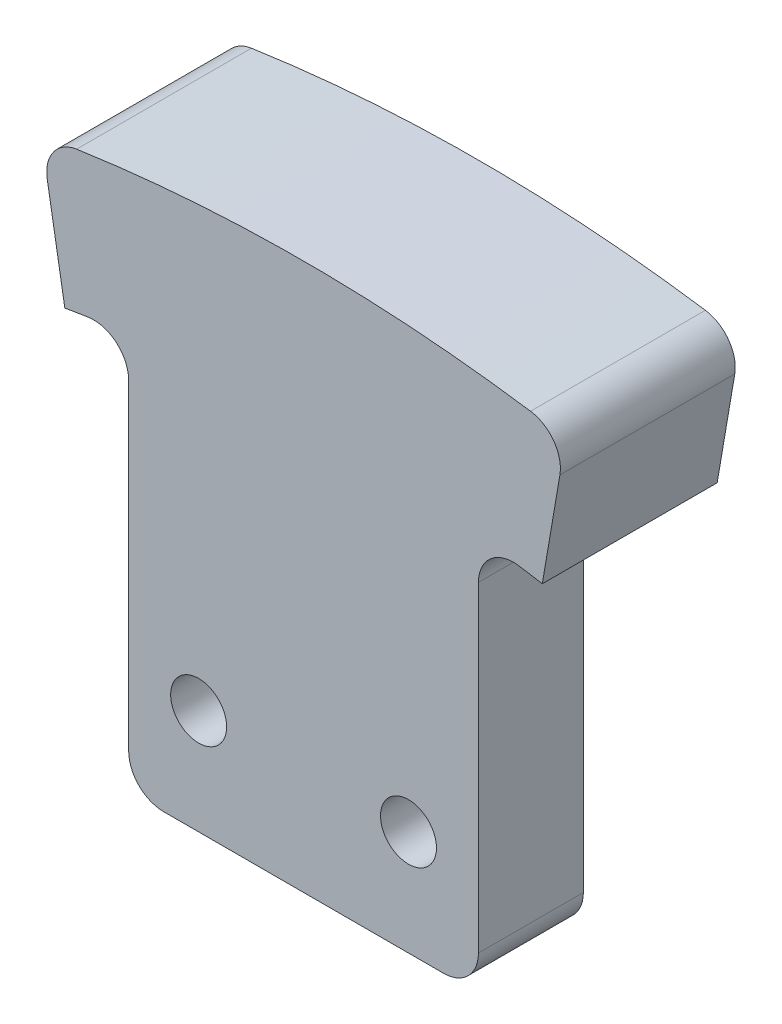
SolidWorks part; units mm, degrees
material "45#"
ref_plane "前视基准面" through (0, 0, 0) normal (0, 0, 1) x (1, 0, 0)
ref_plane "上视基准面" through (0, 0, 0) normal (0, 1, 0) x (1, 0, 0)
ref_plane "右视基准面" through (0, 0, 0) normal (1, 0, 0) x (0, 0, -1)
sketch "草图1" plane through (0, 0, 0) normal (0, 0, 1) x (1, 0, 0)
  line L1 (-5, -7.5) -> (5, -7.5)
  line L2 (-5, -7.5) -> (-5, 7.5)
  line L5 (-5, 7.5) -> (5, 7.5)
  line L6 (5, -7.5) -> (5, 7.5)
  line L7 (-5, -7.5) -> (5, 7.5) construction
  line L8 (-5, 7.5) -> (5, -7.5) construction
  point P0 (0, 0)
  dimension "D1" = 15
  dimension "D2" = 10
extrude "凸台-拉伸1" add sketch "草图1" along normal blind 3
hole_wizard "M2 螺纹孔1" positions "草图4" profile "草图5" tap size "M2" standard "GB" end condition through all
sketch "草图4" plane through (0, 0, 3) normal (0, 0, 1) x (1, 0, 0)
  line L0 (0, -7.5) -> (0, -4.5) construction
  line L1 (-5, -7.5) -> (5, -7.5) construction
  line L3 (-3, -4.5) -> (3, -4.5) construction
  point P0 (3, -4.5)
  point P3 (-3, -4.5)
  point P20 (0, -4.5)
  dimension "D1" = 3
  dimension "D2" = 6
sketch "草图5" plane through (3, -4.5, 3) normal (1, 0, 0) x (0, -1, 0)
  line L0 (0, 0) -> (0, 3)
  line L1 (0, 3) -> (0.8, 3)
  line L2 (0.8, 3) -> (0.8, 0)
  line L5 (0.8, 0) -> (0, 0)
  line L11 (0, -6.35) -> (0, 107.95) construction
  dimension "通孔螺纹孔钻头直径" = 1.6
  dimension "通孔螺纹孔钻头深度" = 3
cosmetic thread "孔螺蚊线3" parameters "D2"=2
cosmetic thread "孔螺蚊线4" parameters "D2"=2
sketch "草图6" plane through (0, 0, 3) normal (0, 0, 1) x (1, 0, 0)
  line L0 (-7.5, 7.5) -> (7.5, 7.5) construction
  line L1 (-7.5, 7.5) -> (-6.8258, 3.5572)
  line L2 (5, 7.5) -> (-5, 7.5) construction
  line L5 (0, 7.5) -> (0, 4.5) construction
  line L7 (7.5, 7.5) -> (6.8258, 3.5572)
  arc A0 (-7.5, 7.5) -> (7.5, 7.5) centre (0, -36.3634) cw
  arc A1 (-6.8258, 3.5572) -> (6.8258, 3.5572) centre (0, -36.3634) cw
  point P3 (0, 7.5)
  point P11 (0, 4.5)
  dimension "D1" = 44.5
  dimension "D2" = 15
  dimension "D3" = 3
  dimension "D4" = 4
extrude "凸台-拉伸4" add sketch "草图6" against normal blind 5
fillet "圆角1" radius 1 5 edges at (0, 4.1366, 0) (-5, 3.8267, 1.5) (5, 3.8267, 1.5) (-7.5, 7.5, 0.5) (7.5, 7.5, 0.5)
fillet "圆角2" radius 1 2 edges at (-5, -7.5, 1.5) (5, -7.5, 1.5)
